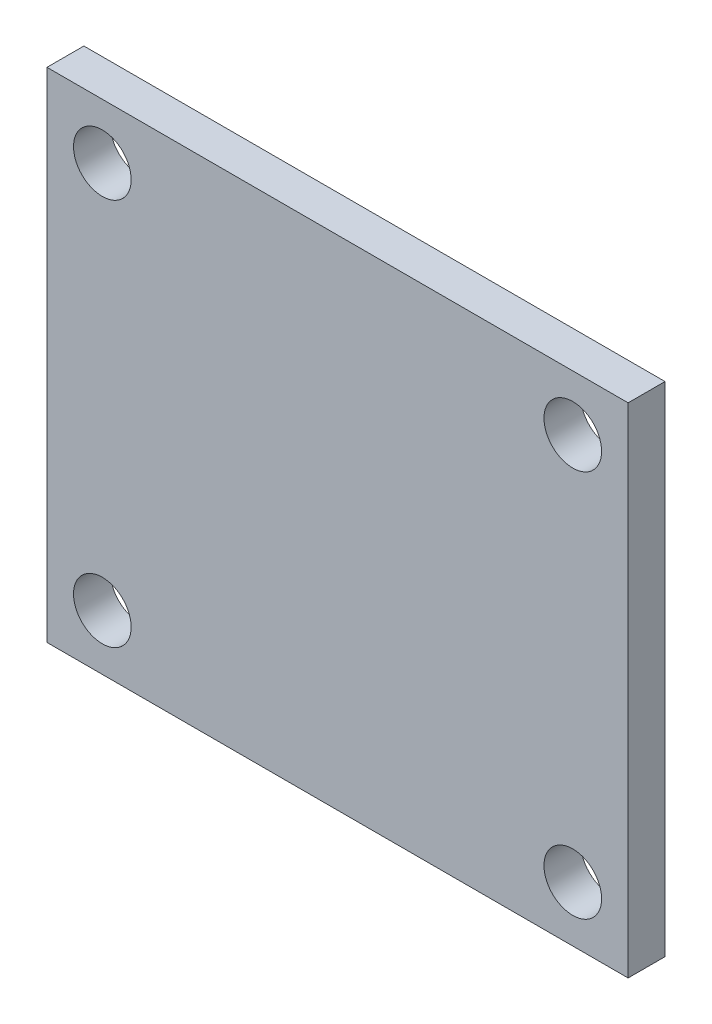
SolidWorks part; units mm, degrees
ref_plane "Front Plane" through (0, 0, 0) normal (0, 0, 1) x (1, 0, 0)
ref_plane "Top Plane" through (0, 0, 0) normal (0, 1, 0) x (1, 0, 0)
ref_plane "Right Plane" through (0, 0, 0) normal (1, 0, 0) x (0, 0, -1)
sketch "Sketch1" plane through (0, 0, 0) normal (0, 0, 1) x (1, 0, 0)
  line L0 (-12.75, -10.5) -> (12.75, 10.5) construction
  line L1 (-15.75, 13.5) -> (15.75, 13.5)
  line L2 (-15.75, 13.5) -> (-15.75, -13.5)
  line L3 (-15.75, -13.5) -> (15.75, -13.5)
  line L4 (15.75, 13.5) -> (15.75, -13.5)
  line L5 (-15.75, 13.5) -> (15.75, -13.5) construction
  line L6 (-15.75, -13.5) -> (15.75, 13.5) construction
  line L8 (-12.75, 10.5) -> (12.75, -10.5) construction
  line L9 (-6, 4) -> (6, 4)
  line L10 (-6, 4) -> (-6, -4)
  line L11 (-6, -4) -> (6, -4)
  line L12 (6, 4) -> (6, -4)
  line L13 (-6, 4) -> (6, -4) construction
  line L14 (-6, -4) -> (6, 4) construction
  circle A0 centre (-12.75, 10.5) radius 1.5625
  circle A1 centre (-12.75, -10.5) radius 1.5625
  circle A2 centre (12.75, 10.5) radius 1.5625
  circle A3 centre (12.75, -10.5) radius 1.5625
  point P0 (0, 0)
  point P15 (0, 0)
  dimension "D3" = 3.125
  dimension "D1" = 31.5
  dimension "D2" = 27
  dimension "D4" = 3
  dimension "D5" = 3
  dimension "D6" = 12
  dimension "D7" = 8
extrude "Boss-Extrude1" add sketch "Sketch1" along normal blind 2 contours L12 L9 L10 L11 | L4 L1 L2 L3 A3 A2 A1 A0 L9 L12 L11 L10 region at (0, 13.0851, 0) region at (0, 0, 0)
extrude "Boss-Extrude2" add sketch "Sketch1<3>" against normal blind 1 contours L12 L9 L10 L11 region at (0, 0, 0)
sketch "Sketch1<3>" plane through (0, 0, 0) normal (0, 0, 1) x (1, 0, 0) same geometry as "Sketch1"
